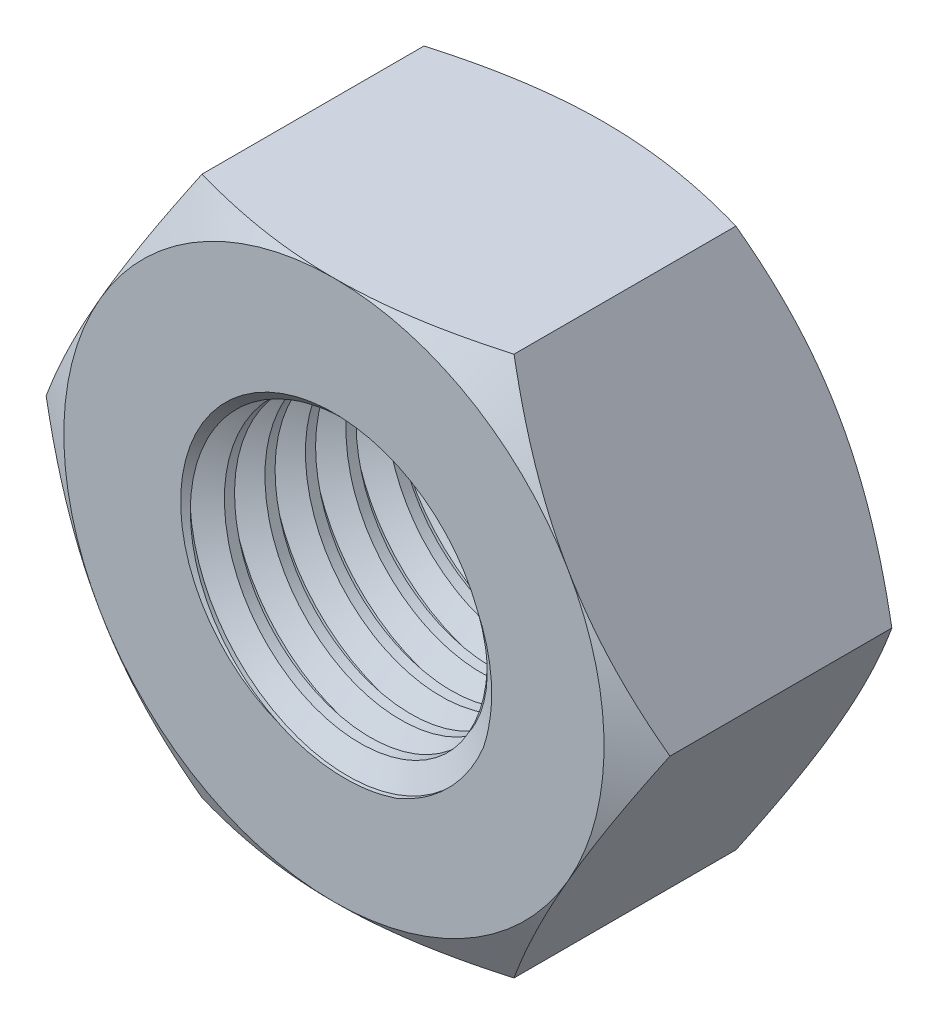
SolidWorks part; units mm, degrees
ref_plane "Front Plane" through (0, 0, 0) normal (0, 0, 1) x (1, 0, 0)
ref_plane "Top Plane" through (0, 0, 0) normal (0, 1, 0) x (1, 0, 0)
ref_plane "Right Plane" through (0, 0, 0) normal (1, 0, 0) x (0, 0, -1)
sketch "Sketch1" plane through (0, 0, 0) normal (0, 0, 1) x (1, 0, 0)
  line L1 (11.547, 0) -> (5.7735, 10)
  line L2 (5.7735, 10) -> (-5.7735, 10)
  line L3 (-5.7735, 10) -> (-11.547, 0)
  line L4 (-11.547, 0) -> (-5.7735, -10)
  line L5 (-5.7735, -10) -> (5.7735, -10)
  line L6 (5.7735, -10) -> (11.547, 0)
  circle A0 centre (0, 0) radius 10 construction
  dimension "D1" = 20
extrude "Boss-Extrude1" add sketch "Sketch1" along normal mid plane 10
sketch "Sketch2" plane through (0, 0, 0) normal (1, 0, 0) x (0, 0, -1)
  line L0 (0, 0) -> (50000, 0) construction
  line L2 (-5, 10) -> (-5, 13)
  line L3 (-5, 13) -> (-3.2679, 13)
  line L4 (-3.2679, 13) -> (-5, 10)
  dimension "D1" = 30
  dimension "D2" = 13
revolve "Cut-Revolve1" cut sketch "Sketch2" angle 360 about L0
mirror "Mirror1" about plane through (0, 0, 0) normal (0, 0, 1) of "Cut-Revolve1"
sketch "Sketch3" plane through (0, 0, 5) normal (0, 0, 1) x (1, 0, 0)
  circle A0 centre (0, 0) radius 5.175
  dimension "D1" = 10.35
extrude "Cut-Extrude1" cut sketch "Sketch3" against normal up to next
chamfer "Chamfer1" distance 0.5 angle 45 2 edges at (5.175, 0, -5) (5.175, 0, 5)
thread "Thread2" pitch 1.5 method cut profile "Thread Profile2" start angle 0, offset 2, length 22, pitch 1.5, diameter 10.35
ref_plane "Plane2" through (-5.175, 0, 6.5) normal (0, -1, 0) x (-1, 0, 0)
sketch "Thread Profile2" plane through (-5.175, 0, 6.5) normal (0, -1, 0) x (-1, 0, 0)
  line L0 (0, 0) -> (0, 1.5) construction
  line L1 (0, 0) -> (0.8119, 0.4687)
  line L2 (0.8119, 0.4687) -> (0.8119, 0.6562)
  line L3 (0.8119, 0.6562) -> (0, 1.125)
  line L4 (0.8119, 0.5625) -> (0, 0.5625) construction
  line L11 (0, 0) -> (0, 1.125)
  point P2 (0, 0)
  dimension "Pitch" = 1.5
  dimension "Profile_Angle" = 60
  dimension "Profile_Land" = 0.1875
  dimension "Profile_Height" = 0.8119
